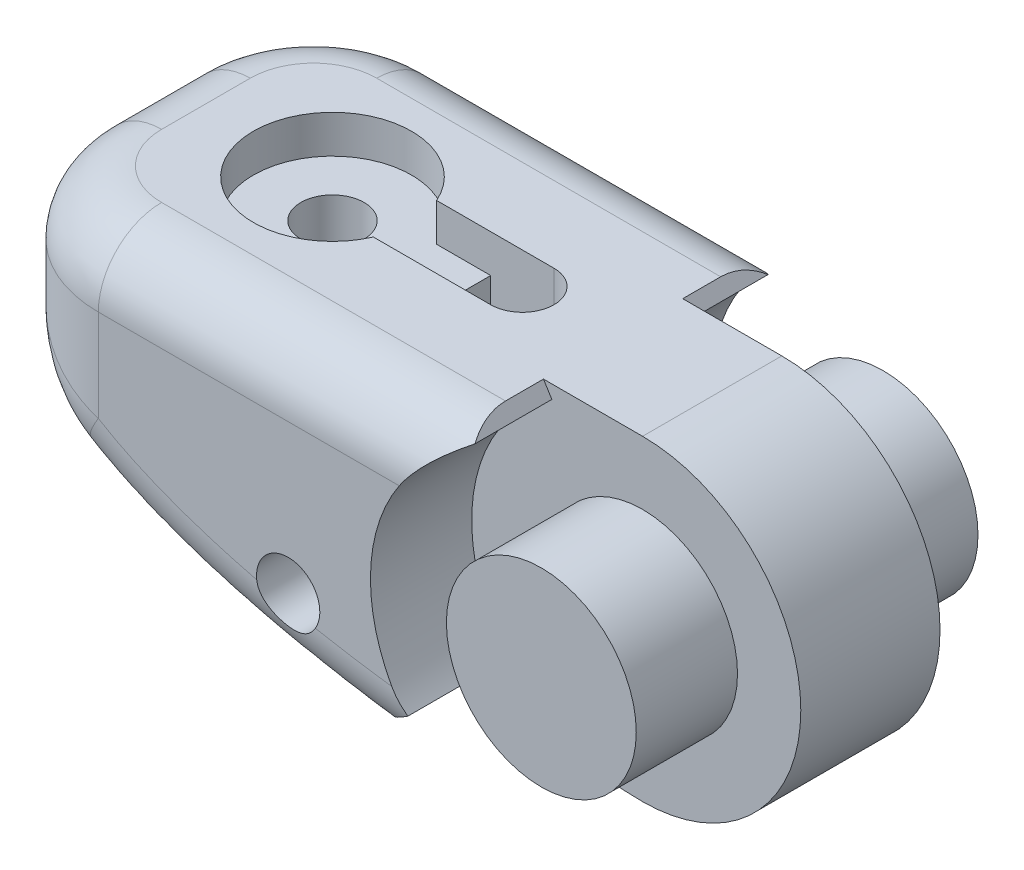
SolidWorks part; units mm, degrees
ref_plane "Front Plane" through (0, 0, 0) normal (0, 0, 1) x (1, 0, 0)
ref_plane "Top Plane" through (0, 0, 0) normal (0, 1, 0) x (1, 0, 0)
ref_plane "Right Plane" through (0, 0, 0) normal (1, 0, 0) x (0, 0, -1)
sketch "Width-Sketch" plane through (0, 0, 0) normal (0, 1, 0) x (1, 0, 0)
  line L0 (0, 0) -> (0, -1.8) construction
  line L1 (0, -1.8) -> (0, -3.6) construction
  line L2 (0, -3.6) -> (0, -5.4) construction
  line L3 (0, -5.4) -> (0, -7.2) construction
  line L4 (0, -7.2) -> (0, -9) construction
  dimension "D1" = 1.8
ref_plane "Centre-Plane" through (0, 0, 5.4) normal (0, 0, 1) x (1, 0, 0)
sketch "Sketch1" plane through (0, 0, 0) normal (0, 0, 1) x (1, 0, 0)
  line L0 (0, 5) -> (-18, 5)
  arc A2 (0, -5) -> (0, 5) centre (0, 0) ccw
  spline S0 degree 3 poles (-18, 5) (-20.8378, -4.4787) (-0.5767, -5.0045) (0, -5) knots 0 0 0 0 1 1 1 1
  dimension "D1" = 5
  dimension "D2" = 18
extrude "Boss-Extrude1" add sketch "Sketch1" along normal up to vertex (5.4 mm away) up to point (0, 0, 5.4)
surface "Surface-Offset1" parameters "D1"=0
sketch "Sketch15" plane through (0, 0, 0) normal (0, 0, -1) x (-1, 0, 0)
  line L0 (2.8667, 4.5763) -> (3.1321, 5)
  line L1 (0, 5) -> (18, 5) construction
  line L2 (3.1321, 5) -> (0.78, 5.3434)
  line L3 (5.9016, -4.4645) -> (4.3065, -3.2579)
  line L4 (5.9016, -4.4645) -> (0.9151, -5.3219)
  arc A0 (4.3065, -3.2579) -> (2.8667, 4.5763) centre (0, 0) ccw
  arc A1 (0, 5) -> (0, -5) centre (0, 0) ccw construction
  circle A2 centre (0, 0) radius 3
  arc A3 (0.78, 5.3434) -> (0.9151, -5.3219) centre (0, 0) ccw
  spline S0 degree 3 poles (18, 5) (20.8378, -4.4787) (0.5767, -5.0045) (0, -5) knots 0 0 0 0 1 1 1 1 construction
  dimension "D2" = 6
  dimension "D1" = 0.4
  dimension "D3" = 0.5
  dimension "D4" = 2
extrude "Cut-Extrude5" cut sketch "Sketch15" against normal blind 3.2
sketch "Sketch16" plane through (0, 0, 5.4) normal (0, 0, -1) x (-1, 0, 0)
  line L0 (7, 0) -> (5, 0)
  line L2 (7, 0) -> (7, -7)
  line L4 (0, -5) -> (0, -7)
  line L5 (0, -7) -> (7, -7)
  arc A1 (0, -5) -> (5, 0) centre (0, 0) ccw
  arc A2 (0, 5) -> (0, -5) centre (0, 0) ccw construction
  dimension "D1" = 2
  dimension "D2" = 2
extrude "Cut-Extrude6" cut sketch "Sketch16" along normal blind 1
sketch "Sketch17" plane through (0, 5, 0) normal (0, 1, 0) x (1, 0, 0)
  line L0 (0, -5.4) -> (-18, -5.4) construction
  line L1 (-7, -5.4) -> (-5, -5.4) construction
  line L2 (-7, -5.4) -> (-5, -5.4) construction
  line L3 (0, -5.4) -> (-18, -5.4) construction
  circle A0 centre (-6, -5.4) radius 1
  point P10 (-6, -5.4)
  dimension "D1" = 2
extrude "Cut-Extrude7" cut sketch "Sketch17" against normal through all
mirror "Mirror1" about plane through (0, 0, 5.4) normal (0, 0, 1) of bodies 117 111
sketch "Sketch18" plane through (0, 5, 0) normal (0, 1, 0) x (1, 0, 0)
  line L0 (-6, -4.4) -> (-9.7087, -4.4)
  line L1 (-6, -4.4) -> (-12, -4.4) construction
  line L2 (-6, -4.4) -> (-6, -6.4)
  line L3 (-6, -6.4) -> (-12, -6.4) construction
  line L4 (-12, -4.4) -> (-12, -6.4) construction
  line L6 (-9.7087, -6.4) -> (-6, -6.4)
  circle A0 centre (-6, -5.4) radius 1 construction
  circle A1 centre (-6, -5.4) radius 1 construction
  arc A2 (-9.7087, -4.4) -> (-9.7087, -6.4) centre (-12, -5.4) ccw
  dimension "D1" = 2.5
  dimension "D2" = 6
extrude "Cut-Extrude8" cut sketch "Sketch18" against normal blind 1.2
sketch "Sketch19" plane through (0, 3.8, 0) normal (0, 1, 0) x (1, 0, 0)
  circle A0 centre (-12, -5.4) radius 1
  arc A1 (-9.7087, -4.4) -> (-9.7087, -6.4) centre (-12, -5.4) ccw construction
  dimension "D1" = 2
extrude "Cut-Extrude9" cut sketch "Sketch19" against normal through all
sketch "Sketch20" plane through (0, 0, 5.4) normal (0, 0, 1) x (1, 0, 0)
  line L0 (-11, 3.8) -> (-13, 3.8) construction
  line L1 (-11, 3.8) -> (-13, 3.8) construction
  line L2 (-11, 3.8) -> (-11, -3.348) construction
  line L3 (-13, 3.8) -> (-13, -2.6393) construction
  line L4 (-12, -6.9171) -> (-10.5, -6.9171)
  line L5 (-10.5, -6.9171) -> (-10.5, -0.912)
  line L6 (-10.5, 2.2) -> (-12, 2.2)
  line L8 (-12, 3.8) -> (-12, -6.9171) construction
  line L9 (-12, -6.9171) -> (-12, 2.2)
  line L10 (-13, -2.6393) -> (-11, -2.6393) construction
  line L11 (-10.5, -2.424) -> (-13.5, -2.424) construction
  line L12 (-10.5, 0.688) -> (-8.5, 0.688)
  line L13 (-8.5, 0.688) -> (-8.5, -0.912)
  line L14 (-8.5, -0.912) -> (-10.5, -0.912)
  line L15 (-10.5, 0.688) -> (-10.5, 2.2)
  line L16 (-11.3066, -2.424) -> (-11.3066, 2.2) construction
  line L17 (-8.5, -0.112) -> (-11.3066, -0.112) construction
  line L18 (-9.7087, 3.8) -> (-14.5, 3.8) construction
  spline S0 degree 3 poles (928.9549, 326.3578) (-1075.1157, -239.6916) (1075.9957, 160.8642) (-998.9607, -121.9414) knots -2.339435 -2.339435 -2.339435 -2.339435 3.468363 3.468363 3.468363 3.468363 only from (-18, 5) to (-5.9016, -4.4645) construction
  spline S1 degree 3 poles (-18, 5) (-19.8553, -1.1971) (-11.837, -3.5674) (-5.9016, -4.4645) knots 0 0 0 0 0.653798 0.653798 0.653798 0.653798 construction
  point P15 (-12, -2.424)
  dimension "D1" = 1.5
  dimension "D2" = 1.6
  dimension "D3" = 1.6
  dimension "D4" = 2
revolve "Cut-Revolve2" cut sketch "Sketch20" angle 360 about L9
sketch "Sketch21" plane through (0, 0.688, 0) normal (0, -1, 0) x (1, 0, 0)
  line L0 (-7, 6.4) -> (-6, 6.4) construction
  line L1 (-8.6459, 6.4) -> (-6, 6.4)
  line L2 (-7, 4.4) -> (-6, 4.4) construction
  line L3 (-8.6459, 4.4) -> (-6, 4.4)
  line L4 (-6, 6.4) -> (-6, 4.4)
  circle A1 centre (-12, 5.4) radius 3.5
  arc A2 (-8.6459, 4.4) -> (-8.6459, 6.4) centre (-12, 5.4) ccw
  dimension "D1" = 0
extrude "Cut-Extrude10" cut sketch "Sketch21" along normal up to surface (1.6 mm away) up to face at (-12, -0.912, 1.9)
sketch "Sketch22" plane through (0, 3.8, 0) normal (0, 1, 0) x (1, 0, 0)
  line L0 (-6, -4.4) -> (-9.7087, -4.4) construction
  line L1 (-8, -4.4) -> (-6, -4.4)
  line L2 (-8, -4.4) -> (-8, -6.4)
  line L3 (-8, -6.4) -> (-6, -6.4)
  line L4 (-6, -4.4) -> (-6, -6.4)
  line L5 (-7, -6.4) -> (-7, -4.4) construction
  line L6 (-7, -6.4) -> (-7, -4.4) construction
  dimension "D1" = 1
extrude "Cut-Extrude11" cut sketch "Sketch22" against normal through all both and the other way through all
sketch "Sketch23" plane through (0, 0, 4.4) normal (0, 0, 1) x (1, 0, 0)
  line L0 (-8, -4.0957) -> (-8, -0.912) construction
  line L1 (-8, -1.712) -> (-8, -0.912) construction
  line L2 (-8, -0.912) -> (-7.2, -0.912) construction
  line L3 (-8, -4.0957) -> (-8, -0.912) construction
  line L9 (-7.2, -0.912) -> (-7.2, -1.712) construction
  line L10 (-7.2, -1.712) -> (-8, -1.712) construction
  circle A0 centre (-8, -1.712) radius 1
  dimension "D1" = 2
  dimension "D2" = 0.8
extrude "Cut-Extrude12" cut sketch "Sketch23" against normal through all both and the other way through all
sketch "Sketch24" plane through (0, 5, 0) normal (0, 1, 0) x (1, 0, 0)
  line L0 (-18, -6.8) -> (-18, -4)
  line L1 (-14, -10.8) -> (-24.8, -10.8)
  line L2 (-24.8, -10.8) -> (-24.8, 0)
  line L3 (-24.8, 0) -> (-14, 0)
  line L4 (-18, -10.8) -> (-18, 0) construction
  line L5 (-3.1321, 0) -> (-18, 0) construction
  line L6 (-3.1321, -10.8) -> (-18, -10.8) construction
  arc A0 (-18, -4) -> (-14, 0) centre (-14, -4) cw
  arc A1 (-18, -6.8) -> (-14, -10.8) centre (-14, -6.8) ccw
  dimension "D2" = 4
extrude "Cut-Extrude13" cut sketch "Sketch24" against normal through all
fillet "Fillet1" radius 2 10 edges at (-8.566, 5, 0) (-16.8284, 5, 1.1716) (-18, 5, 5.4) (-16.8284, 5, 9.6284) (-8.566, 5, 10.8) (-17.5795, 0.7721, 8.5853) (-18, 1.6532, 5.4) (-17.7563, 1.0894, 2.6251)
equation "\"Ligament\"=2"
equation "\"Clearance\"=0.4"
equation "\"D1@Sketch15\"=\"Clearance\""
equation "\"D1@Sketch17\"=\"Ligament\""
equation "\"D1@Sketch16\"=\"Ligament\""
equation "\"D1@Cut-Extrude6\"=\"Ligament\"/2"
equation "\"D1@Cut-Extrude8\"=\"Ligament\"/2"
equation "\"Trim\"=0.5"
equation "\"D3@Sketch15\"=\"Trim\""
equation "\"D4@Sketch15\"=\"Trim\"*4"
equation "\"D2@Sketch23\"=\"Clearance\"*2"
equation "\"D1@Width-Sketch\"    = \"Ligament\"*0.9"
